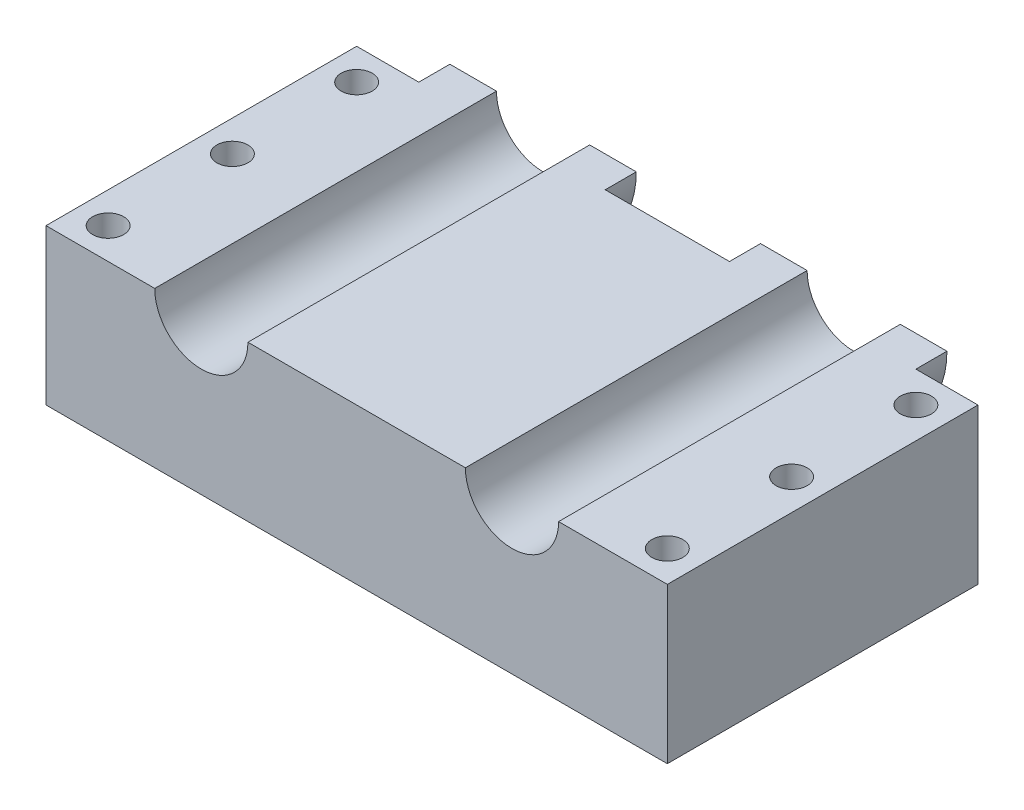
SolidWorks part; units mm, degrees
ref_plane "Front Plane" through (0, 0, 0) normal (0, 0, 1) x (1, 0, 0)
ref_plane "Top Plane" through (0, 0, 0) normal (0, 1, 0) x (1, 0, 0)
ref_plane "Right Plane" through (0, 0, 0) normal (1, 0, 0) x (0, 0, -1)
sketch "Sketch1" plane through (0, 0, 0) normal (0, 1, 0) x (1, 0, 0)
  line L1 (0, 0) -> (254, 0)
  line L2 (0, 0) -> (0, -127)
  line L3 (0, -127) -> (254, -127)
  line L4 (254, 0) -> (254, -127)
  circle A0 centre (12.7, -12.7) radius 6.35
  circle A1 centre (241.3, -12.7) radius 6.35
  circle A2 centre (241.3, -63.5) radius 6.35
  circle A3 centre (241.3, -114.3) radius 6.35
  circle A4 centre (12.7, -63.5) radius 6.35
  circle A5 centre (12.7, -114.3) radius 6.35
  dimension "D3" = 12.7
  dimension "D1" = 254
  dimension "D2" = 127
  dimension "D6" = 50.8
  dimension "D7" = 228.6
  dimension "D8" = 12.7
  dimension "D9" = 12.7
  dimension "D4" = 2
  dimension "D5" = 3
extrude "Boss-Extrude3" add sketch "Sketch1" along normal blind 63.5 contours A4 | A0 | A1 | A2 | A3 | L2 L3 L4 L1 | A5 region at (12.7, 0, 12.7) region at (241.3, 0, 12.7) region at (241.3, 0, 63.5) region at (241.3, 0, 114.3) region at (12.7, 0, 63.5)
sketch "Sketch3" plane through (0, 0, 0) normal (0, 0, -1) x (-1, 0, 0)
  line L0 (0, 63.5) -> (-254, 63.5) construction
  line L1 (-101.6, 63.5) -> (-25.4, 63.5)
  line L2 (-127, 0) -> (-127, 63.5) construction
  line L3 (0, 0) -> (-254, 0) construction
  line L5 (-152.4, 63.5) -> (-228.6, 63.5)
  arc A2 (-209.55, 63.5) -> (-171.45, 63.5) centre (-190.5, 63.5) ccw
  arc A3 (-228.6, 63.5) -> (-152.4, 63.5) centre (-190.5, 63.5) ccw
  arc A4 (-25.4, 63.5) -> (-101.6, 63.5) centre (-63.5, 63.5) cw
  arc A5 (-44.45, 63.5) -> (-82.55, 63.5) centre (-63.5, 63.5) cw
  line M7 (0, 63.5) -> (-254, 63.5)
extrude "Boss-Extrude9" add sketch "Sketch3" along normal blind 12.7 contours A3 A2 M7 | A5 A4 M7 region at (92.075, 62.6481, 0) region at (190.5, 26.2519, 0)
extrude "Cut-Extrude5" cut sketch "Sketch3<12>" against normal through all and the other way through all contours A5 L1 | L5 A2 region at (63.5, 55.4149, 0) region at (190.5, 55.4149, 0)
sketch "Sketch3<12>" plane through (0, 0, 0) normal (0, 0, -1) x (-1, 0, 0) same geometry as "Sketch3"
